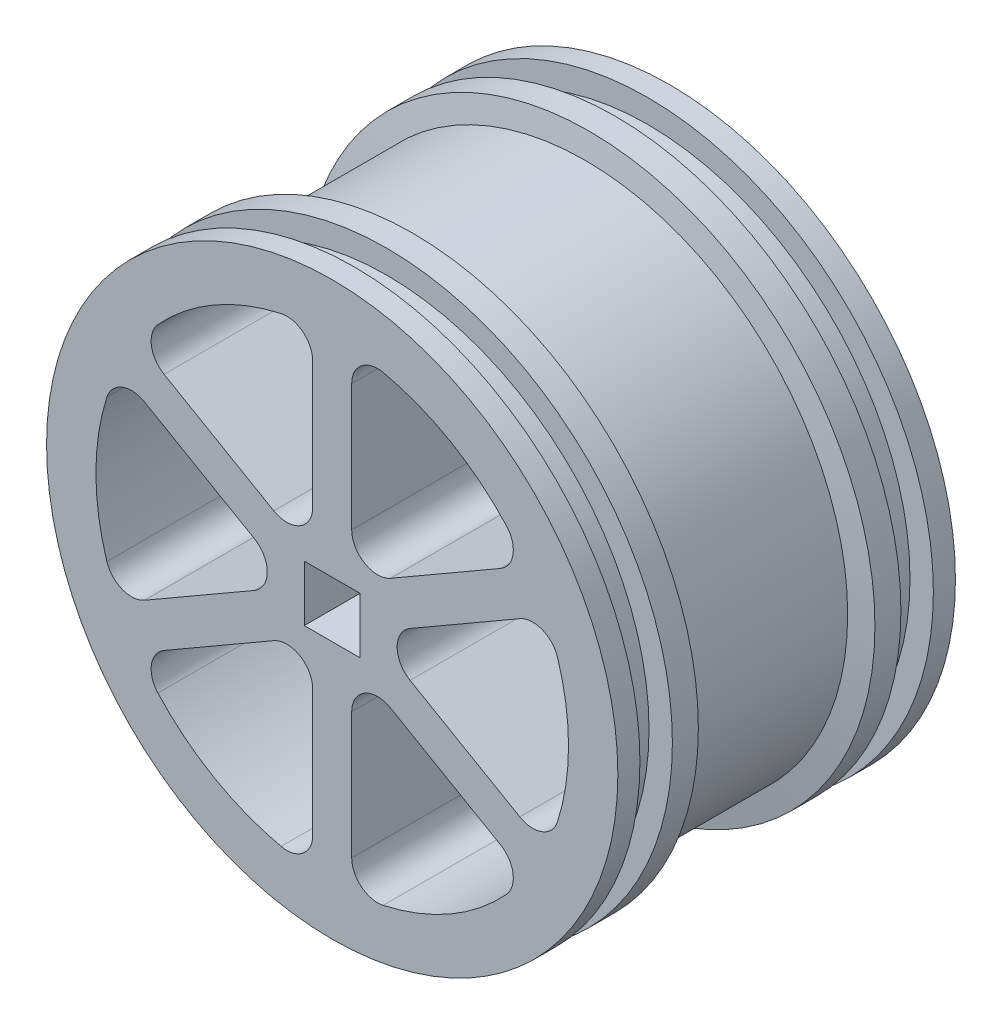
SolidWorks part; units mm, degrees
ref_plane "Front Plane" through (0, 0, 0) normal (0, 0, 1) x (1, 0, 0)
ref_plane "Top Plane" through (0, 0, 0) normal (0, 1, 0) x (1, 0, 0)
ref_plane "Right Plane" through (0, 0, 0) normal (1, 0, 0) x (0, 0, -1)
sketch "Sketch1" plane through (0, 0, 0) normal (1, 0, 0) x (0, 0, -1)
  line L1 (0, 22) -> (1.7, 22)
  line L2 (1.7, 22) -> (1.7, 20.2)
  line L3 (1.7, 20.2) -> (4.2, 20.2)
  line L4 (4.2, 20.2) -> (4.2, 22)
  line L5 (4.2, 22) -> (6.2, 22)
  line L6 (6.2, 22) -> (6.5, 20.2)
  line L7 (19.8, 22) -> (19.5, 20.2)
  line L8 (19.5, 20.2) -> (6.5, 20.2)
  line L10 (0, 18.2) -> (26, 18.2)
  line L11 (19.8, 22) -> (21.8, 22)
  line L12 (21.8, 22) -> (21.8, 20.2)
  line L13 (21.8, 20.2) -> (24.3, 20.2)
  line L14 (24.3, 20.2) -> (24.3, 22)
  line L15 (24.3, 22) -> (26, 22)
  line L18 (-0.3222, 0) -> (27.2819, 0) construction
  line L19 (0, 0) -> (0, 18.2) construction
  line L20 (0, 22) -> (0, 1028.7814) construction
  line L21 (0, 22) -> (0, 18.2)
  line L22 (26, 22) -> (26, 18.2)
  dimension "D1" = 22
  dimension "D2" = 1.7
  dimension "D3" = 2
  dimension "D4" = 0.3
  dimension "D5" = 2.3
  dimension "D6" = 3.8
  dimension "D7" = 1.8
  dimension "D8" = 2.5
  dimension "D9" = 26
revolve "Revolve1" add sketch "Sketch1" angle 360 about L18
sketch "Sketch2" plane through (0, 0, 0) normal (0, 0, 1) x (1, 0, 0)
  line L0 (0, 0) -> (0, 18.2) construction
  line L1 (-1.5, 18.2) -> (-1.5, 0)
  line L2 (-1.5, 18.2) -> (1.5, 18.2)
  line L3 (-1.5, 0) -> (1.5, 0)
  line L4 (1.5, 18.2) -> (1.5, 0)
  line L5 (-1.5, 18.2) -> (1.5, 0) construction
  line L6 (-1.5, 0) -> (1.5, 18.2) construction
  circle A0 centre (0, 0) radius 18.2 construction
  point P6 (0, 9.1)
  dimension "D1" = 18.2
  dimension "D2" = 3
extrude "Boss-Extrude1" add sketch "Sketch2" against normal blind 24
pattern_circular "CirPattern1" count 6 over 360 about axis through (0, 0, 0) along (0, 0, 1) of "Boss-Extrude1"
sketch "Sketch3" plane through (0, 0, 0) normal (0, 0, 1) x (1, 0, 0)
  line L1 (-2.15, -2.15) -> (2.15, -2.15)
  line L2 (-2.15, -2.15) -> (-2.15, 2.15)
  line L3 (-2.15, 2.15) -> (2.15, 2.15)
  line L4 (2.15, -2.15) -> (2.15, 2.15)
  line L5 (-2.15, -2.15) -> (2.15, 2.15) construction
  line L6 (-2.15, 2.15) -> (2.15, -2.15) construction
  point P0 (0, 0)
  dimension "D1" = 4.3
extrude "Cut-Extrude1" cut sketch "Sketch3" against normal through all both and the other way through all
fillet "Fillet1" radius 2 18 edges at (-14.958, 10.3681, -12) (16.458, -7.77, -12) (-1.5, 18.1381, -12) (-1.5, 2.5981, -12) (1.5, 18.1381, -12) (14.958, 10.3681, -12) (1.5, 2.5981, -12) (16.458, 7.77, -12) (3, 0, -12) (1.5, -2.5981, -12) (14.958, -10.3681, -12) (1.5, -18.1381, -12) (-1.5, -2.5981, -12) (-1.5, -18.1381, -12) (-14.958, -10.3681, -12) (-16.458, -7.77, -12) (-16.458, 7.77, -12) (-3, 0, -12)
fillet "Fillet2" radius 2 1 edges at (18.2, 0, -26)
